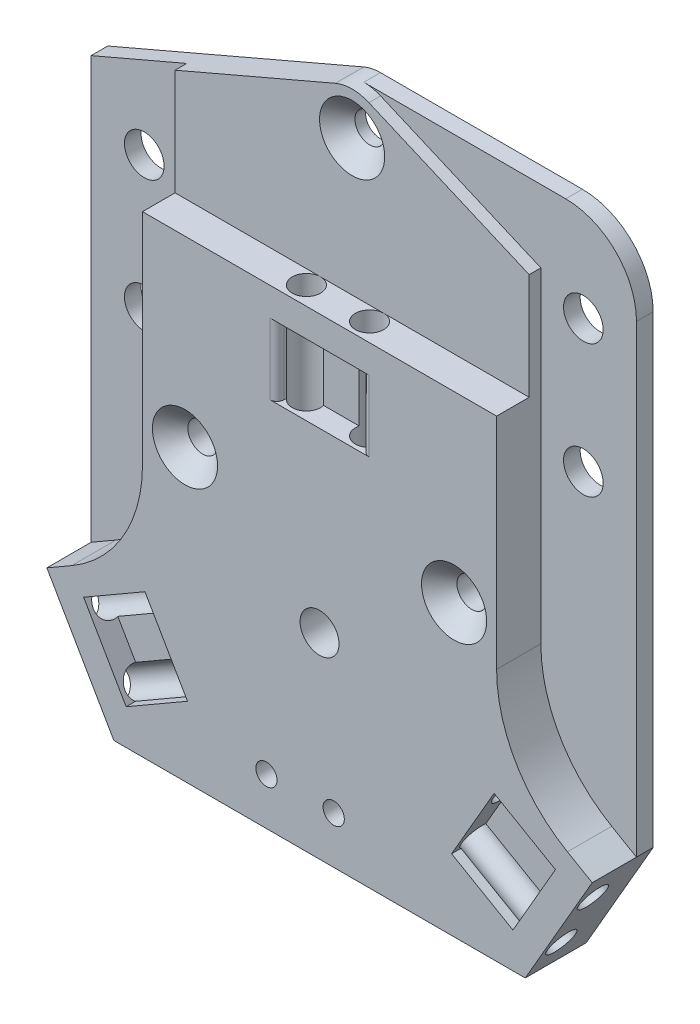
SolidWorks part; units mm, degrees
other "carriage coupler plate"
material "PET"
ref_plane "Front" through (0, 0, 0) normal (0, 0, 1) x (1, 0, 0)
ref_plane "Top" through (0, 0, 0) normal (0, 1, 0) x (1, 0, 0)
ref_plane "Right" through (0, 0, 0) normal (1, 0, 0) x (0, 0, -1)
sketch "Sketch1" plane through (0, 0, 0) normal (0, 0, 1) x (1, 0, 0)
  line L0 (0, 0) -> (0, 30) construction
  line L1 (0, 0) -> (25.9808, -15) construction
  line L2 (0, 0) -> (-25.9808, -15) construction
  dimension "D1" = 120
  dimension "D2" = 120
  dimension "D3" = 30
ref_plane "Plane1" through (0, 30, 0) normal (0, 1, 0) x (1, 0, 0)
sketch "Sketch2" plane through (0, 30, 0) normal (0, 1, 0) x (1, 0, 0)
  line L0 (-4.4589, 0) -> (0, -4.0148) construction
  line L1 (0, 0) -> (-25.9808, 0) construction
  line L2 (0, 0) -> (0, -4.0148) construction
  line L3 (-4.4589, 0) -> (0, 0) construction
  line L4 (0, -5.3962) -> (0, -4.0148) construction
  line L5 (0, -5.3962) -> (-4.4589, 0) construction
  line L7 (-4, -4.0148) -> (4, -4.0148) construction
  line L8 (3.9519, -3.3962) -> (-3.9519, -3.3962) construction
  line L9 (0, -0.3962) -> (0, -3.3962) construction
  line L10 (0, -4.0148) -> (0, -7.3926) construction
  circle A0 centre (-4.4589, 0) radius 2
  circle A1 centre (4.4589, 0) radius 2
  circle A2 centre (0, -4.0148) radius 4
  circle A3 centre (0, -5.3962) radius 5 construction
  circle A4 centre (0, -7.3926) radius 1.5
  dimension "D1" = 4
  dimension "D2" = 8
  dimension "D4" = 10
  dimension "D9" = 3
  dimension "D6" = 7.3926
  dimension "D8" = 8.9177
  dimension "D3" = 42
  dimension "D5" = 50.433
  dimension "D7" = 3.3962
  dimension "D10" = 0.6186
sketch "Sketch3" plane through (0, 0, 0) normal (0, 0, 1) x (1, 0, 0)
  line L0 (0, 30) -> (0, 35) construction
  line L2 (0, 35) -> (0, 39) construction
  line L3 (-25, 39) -> (25, 39)
  line L4 (25, 39) -> (25, -3.5116)
  line L5 (25, -3.5116) -> (38.5044, -11.3084)
  line L6 (0, 0) -> (0, 30) construction
  line L7 (-25, -3.5116) -> (-38.5044, -11.3084)
  line L8 (-25, 39) -> (-25, -3.5116)
  line L9 (4.4589, 30) -> (4.4589, 39) construction
  line L10 (25.9808, -15) -> (33.775, -19.5) construction
  line L11 (29.0456, -27.6916) -> (-29.0456, -27.6916)
  line L13 (0, 0) -> (25.9808, -15) construction
  line L14 (33.775, -19.5) -> (38.5044, -11.3084)
  line L15 (4.4589, 30) -> (0, 30) construction
  line L16 (4.4589, 30) -> (9.4589, 30) construction
  line L17 (-33.775, -19.5) -> (-38.5044, -11.3084)
  line L18 (33.775, -19.5) -> (29.0456, -27.6916)
  line L19 (-33.775, -19.5) -> (-29.0456, -27.6916)
  dimension "D1" = 5
  dimension "D2" = 4
  dimension "D3" = 25
  dimension "D4" = 120
  dimension "D5" = 5
  dimension "D6" = 9.4589
  dimension "D7" = 9.4589
  dimension "D8" = 9
  dimension "D9" = 9
extrude "Boss-Extrude1" add sketch "Sketch3" along normal blind 2.6 and the other way blind 6
fillet "Fillet1" radius 20 2 edges at (-25, -3.5116, -1.7) (25, -3.5116, -1.7)
sketch "Sketch4" plane through (0, 30, 0) normal (0, 1, 0) x (1, 0, 0)
  line L0 (0, -0.0148) -> (0, 0.4852) construction
  line L1 (5.1148, 0.4852) -> (-5.1148, 0.4852)
  line L2 (-5.1148, 0.4852) -> (-6, -0.4)
  line L3 (-6, -0.4) -> (-6, -2.6)
  line L4 (25, -2.6) -> (-25, -2.6) construction
  line L5 (-6, -2.6) -> (6, -2.6)
  line L7 (0, -5.3962) -> (-4.4589, 0) construction
  line L8 (-0.7342, -4.5076) -> (-0.5833, -4.3426)
  line L9 (6, -0.4) -> (6, -2.6)
  line L10 (5.1148, 0.4852) -> (6, -0.4)
  circle A7 centre (0, -4.0148) radius 4 construction
  dimension "D1" = 0.5
  dimension "D2" = 135
  dimension "D3" = 12
  dimension "D4" = 2.2
extrude "Cut-Extrude1" cut sketch "Sketch4" against normal blind 5 and the other way blind 5 contours L5 L9 L10 L1 L2 L3
sketch "Sketch5" plane through (0, 39, 0) normal (0, 1, 0) x (1, 0, 0)
  circle A0 centre (-4.4589, 0) radius 2 construction
  circle A1 centre (4.4589, 0) radius 2 construction
  circle A2 centre (-4.4589, 0) radius 2
  circle A3 centre (4.4589, 0) radius 2
extrude "Cut-Extrude2" cut sketch "Sketch5" against normal blind 20
fillet "Fillet3" radius 1 2 edges at (-6, 30, 2.6) (6, 30, 2.6)
ref_axis "Axis1" through (0, 0, -80.9) along (0, 0, 1)
pattern_circular "CirPattern1" count 3 over 360 about axis through (0, 0, -80.9) along (0, 0, 1) of "Cut-Extrude2", "Cut-Extrude1"
sketch "Sketch6" plane through (0, 0, 2.6) normal (0, 0, 1) x (1, 0, 0)
  circle A0 centre (0, 0) radius 2.75
  dimension "D1" = 5.5
extrude "Cut-Extrude3" cut sketch "Sketch6" against normal through all
sketch "Sketch7" plane through (0, 0, -6) normal (0, 0, -1) x (-1, 0, 0)
  line L2 (0, 0) -> (0, 58.2) construction
  line L3 (-25, 39) -> (25, 39) construction
  line L4 (-25, 39) -> (25, 39)
  line L5 (-25, 39) -> (-25, 54)
  line L6 (-25, 54) -> (-2.3663, 63.7137)
  line L7 (25, 39) -> (25, 54)
  line L8 (25, 54) -> (2.3663, 63.7137)
  arc A0 (2.3663, 63.7137) -> (-2.3663, 63.7137) centre (0, 58.2) ccw
  point P14 (0, 0)
  dimension "D1" = 12
  dimension "D2" = 19.2
  dimension "D3" = 15
extrude "Boss-Extrude2" add sketch "Sketch7" against normal blind 4
sketch "Sketch8" plane through (0, 0, 2.6) normal (0, 0, 1) x (1, 0, 0)
  line L0 (0, 0) -> (0, 58.2) construction
  line L1 (-19, 13.2) -> (19, 13.2) construction
  circle A0 centre (-19, 13.2) radius 2.1
  circle A1 centre (19, 13.2) radius 2.1
  circle A2 centre (0, 58.2) radius 2.1
  arc A3 (2.3663, 63.7137) -> (-2.3663, 63.7137) centre (0, 58.2) ccw construction
  point P10 (0, 13.2)
  dimension "D1" = 4.2
  dimension "D2" = 4.2
  dimension "D3" = 4.2
  dimension "D4" = 45
  dimension "D5" = 38
extrude "Cut-Extrude4" cut sketch "Sketch8" against normal through all
chamfer "Chamfer1" distance 2.5 angle 45 3 edges at (-16.9, 13.2, 2.6) (21.1, 13.2, 2.6) (-2.1, 58.2, -2)
sketch "Sketch9" plane through (0, 0, -6) normal (0, 0, -1) x (-1, 0, 0)
  line L0 (0, -27.6916) -> (0, -6.1064) construction
  line L1 (29.0456, -27.6916) -> (-29.0456, -27.6916) construction
  line L2 (-2, -21.0416) -> (7.5, -21.0416) construction
  circle A0 centre (7.5, -21.0416) radius 1.5
  circle A1 centre (-2, -21.0416) radius 1.5
  dimension "D4" = 3
  dimension "D5" = 3
  dimension "D1" = 6.65
  dimension "D2" = 7.5
  dimension "D3" = 9.5
extrude "Cut-Extrude5" cut sketch "Sketch9" against normal through all
sketch "Sketch10" plane through (0, 0, -6) normal (0, 0, -1) x (-1, 0, 0)
  line L0 (25, 54) -> (38.5044, 48.2043)
  line L2 (25, 8.0354) -> (25, 54)
  line L4 (38.5044, -11.3084) -> (38.5044, 48.2043)
  line L7 (38.5044, -11.3084) -> (38.5044, 22.7) construction
  line L8 (35, -9.2851) -> (38.5044, -11.3084)
  line L9 (25, 54) -> (2.3663, 63.7137) construction
  arc A2 (35, -9.2851) -> (25, 8.0354) centre (45, 8.0354) cw
extrude "Boss-Extrude3" add sketch "Sketch10" against normal blind 2.35
sketch "Sketch11" plane through (0, 0, -6) normal (0, 0, -1) x (-1, 0, 0)
  line L0 (-38.5044, -11.3084) -> (-38.5044, 64.2)
  line L2 (-38.5044, -11.3084) -> (-35, -9.2851)
  line L3 (-25, 8.0354) -> (-25, 54)
  line L7 (0, 64.2) -> (-38.5044, 64.2)
  line L8 (-25, 54) -> (-2.3663, 63.7137)
  line L9 (-2.3663, 63.7137) -> (-25, 54) construction
  arc A2 (-35, -9.2851) -> (-25, 8.0354) centre (-45, 8.0354) ccw
  arc A4 (2.3663, 63.7137) -> (-2.3663, 63.7137) centre (0, 58.2) ccw construction
  arc A5 (-2.3663, 63.7137) -> (0, 64.2) centre (0, 58.2) cw
extrude "Boss-Extrude4" add sketch "Sketch11" against normal blind 2.35
sketch "Sketch12" plane through (0, 0, -3.65) normal (0, 0, 1) x (1, 0, 0)
  line L0 (-38.5044, 39.8275) -> (-31, 39.8275) construction
  line L1 (-38.5044, -11.3084) -> (-38.5044, 48.2043) construction
  line L2 (38.5044, 50.8275) -> (31, 50.8275) construction
  line L3 (38.5044, 64.2) -> (38.5044, -11.3084) construction
  line L4 (25, 8.0354) -> (25, 54) construction
  line L5 (-25, 54) -> (-25, 8.0354) construction
  line L6 (25, 39) -> (-25, 39) construction
  line L7 (-31, 39.8275) -> (-31, 21.0775) construction
  line L8 (25, 39) -> (4.4589, 39) construction
  line L9 (31, 50.8275) -> (31, 32.0775) construction
  circle A0 centre (-31, 39.8275) radius 2.8
  circle A1 centre (31, 50.8275) radius 2.8
  circle A2 centre (-31, 21.0775) radius 2.8
  circle A3 centre (31, 32.0775) radius 2.8
  dimension "D5" = 5.6
  dimension "D6" = 5.6
  dimension "D7" = 5.6
  dimension "D9" = 5.6
  dimension "D1" = 0.8275
  dimension "D2" = 11.8275
  dimension "D3" = 6
  dimension "D4" = 6
  dimension "D8" = 18.75
  dimension "D10" = 18.75
extrude "Cut-Extrude6" cut sketch "Sketch12" against normal blind 2.35
fillet "Fillet4" radius 10 1 edges at (38.5044, 64.2, -4.825)
